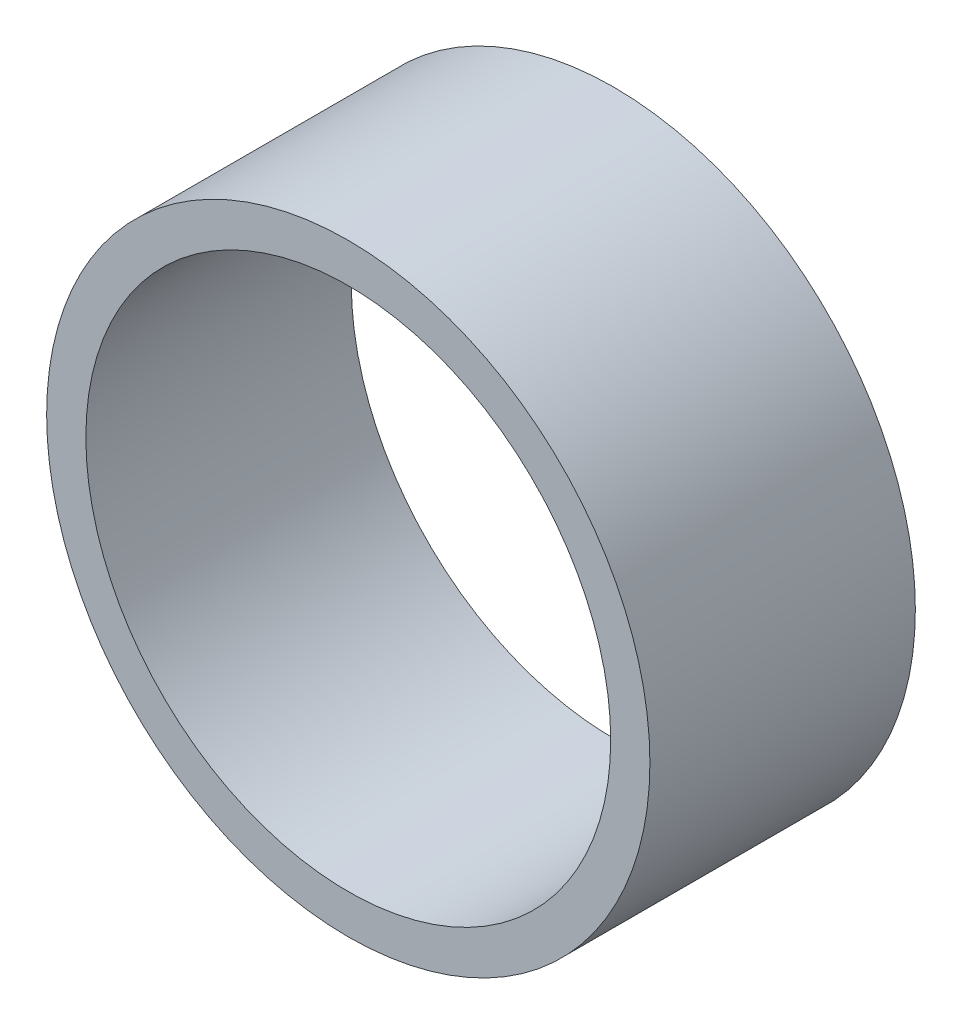
SolidWorks part; units mm, degrees
material "Plain Carbon Steel"
ref_plane "Front Plane" through (0, 0, 0) normal (0, 0, 1) x (1, 0, 0)
ref_plane "Top Plane" through (0, 0, 0) normal (0, 1, 0) x (1, 0, 0)
ref_plane "Right Plane" through (0, 0, 0) normal (1, 0, 0) x (0, 0, -1)
sketch "Sketch1" plane through (0, 0, 0) normal (0, 0, 1) x (1, 0, 0)
  circle A0 centre (0, 0) radius 21.75
  circle A1 centre (0, 0) radius 25
  dimension "D1" = 50
  dimension "D2" = 43.5
extrude "Boss-Extrude1" add sketch "Sketch1" along normal mid plane 22
